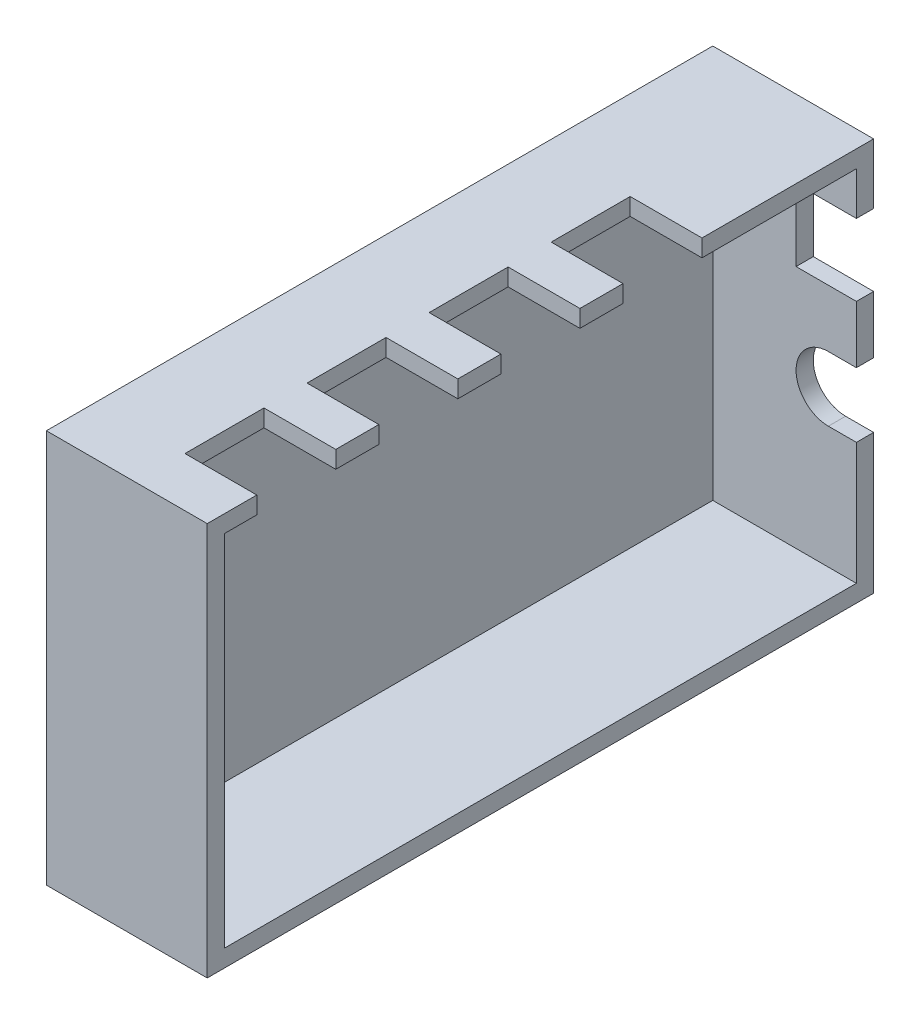
SolidWorks part; units mm, degrees
ref_plane "Front Plane" through (0, 0, 0) normal (0, 0, 1) x (1, 0, 0)
ref_plane "Top Plane" through (0, 0, 0) normal (0, 1, 0) x (1, 0, 0)
ref_plane "Right Plane" through (0, 0, 0) normal (1, 0, 0) x (0, 0, -1)
sketch "Sketch1" plane through (16.0375, 0, 0) normal (-1, 0, 0) x (0, 0, 1)
  line L1 (13.8883, 37.3092) -> (57.8883, 37.3092)
  line L2 (13.8883, 37.3092) -> (13.8883, 12.3092)
  line L3 (13.8883, 12.3092) -> (57.8883, 12.3092)
  line L4 (57.8883, 37.3092) -> (57.8883, 12.3092)
extrude "Boss-Extrude1" add sketch "Sketch1" along normal blind 10
shell "Shell1" thickness 1.2 removed face at (16.0375, 24.8092, 35.8883) outward yes
sketch "Sketch2" plane through (0, 38.5092, 0) normal (0, 1, 0) x (1, 0, 0)
  line L0 (16.0375, -55.6383) -> (21.0375, -55.6383) construction
  line L1 (16.0375, -55.6383) -> (21.0375, -55.6383) construction
  line L2 (21.0375, -50.1383) -> (16.0375, -50.1383) construction
  line L3 (21.0375, -50.1383) -> (16.0375, -50.1383) construction
  line L4 (16.0375, -59.0883) -> (16.0375, -12.6883)
  line L5 (16.0375, -12.6883) -> (4.8375, -12.6883)
  line L6 (4.8375, -12.6883) -> (4.8375, -59.0883)
  line L7 (4.8375, -59.0883) -> (16.0375, -59.0883)
  line L8 (16.0375, -59.0883) -> (16.0375, -12.6883)
  line L9 (16.0375, -12.6883) -> (4.8375, -12.6883)
  line L10 (4.8375, -12.6883) -> (4.8375, -59.0883)
  line L11 (4.8375, -59.0883) -> (16.0375, -59.0883)
  line L12 (21.0375, -41.6383) -> (16.0375, -41.6383) construction
  line L13 (21.0375, -41.6383) -> (16.0375, -41.6383) construction
  line L14 (16.0375, -47.1383) -> (21.0375, -47.1383) construction
  line L15 (16.0375, -47.1383) -> (21.0375, -47.1383) construction
  line L16 (16.0375, -38.6383) -> (21.0375, -38.6383) construction
  line L17 (16.0375, -38.6383) -> (21.0375, -38.6383) construction
  line L18 (21.0375, -33.1383) -> (16.0375, -33.1383) construction
  line L19 (21.0375, -33.1383) -> (16.0375, -33.1383) construction
  line L20 (16.0375, -30.1383) -> (21.0375, -30.1383) construction
  line L21 (16.0375, -30.1383) -> (21.0375, -30.1383) construction
  line L22 (21.0375, -24.6383) -> (16.0375, -24.6383) construction
  line L23 (21.0375, -24.6383) -> (16.0375, -24.6383) construction
  line L24 (16.0375, -55.6383) -> (11.0375, -55.6383)
  line L25 (11.0375, -55.6383) -> (11.0375, -50.1383)
  line L26 (11.0375, -50.1383) -> (16.0375, -50.1383)
  line L27 (16.0375, -47.1383) -> (11.0375, -47.1383)
  line L28 (11.0375, -47.1383) -> (11.0375, -41.6383)
  line L29 (11.0375, -41.6383) -> (16.0375, -41.6383)
  line L30 (16.0375, -38.6383) -> (11.0375, -38.6383)
  line L31 (11.0375, -38.6383) -> (11.0375, -33.1383)
  line L32 (11.0375, -33.1383) -> (16.0375, -33.1383)
  line L33 (16.0375, -30.1383) -> (11.0375, -30.1383)
  line L34 (11.0375, -30.1383) -> (11.0375, -24.6383)
  line L35 (11.0375, -24.6383) -> (16.0375, -24.6383)
  line L36 (16.0375, -30.1383) -> (16.0375, -24.6383)
  line L37 (16.0375, -38.6383) -> (16.0375, -33.1383)
  line L38 (16.0375, -47.1383) -> (16.0375, -41.6383)
  line L39 (16.0375, -55.6383) -> (16.0375, -50.1383)
  dimension "D1" = 0
extrude "Cut-Extrude1" cut sketch "Sketch2" against normal up to surface (1.2 mm away) contours L26 L25 L24 L8 | L29 L28 L27 L8 | L32 L31 L30 L8 | L35 L34 L33 L8 region at (13.5375, 38.5092, 52.8883) region at (13.5375, 38.5092, 44.3883) region at (13.5375, 38.5092, 27.3883) region at (13.5375, 38.5092, 35.8883) up to face at (11.0375, 37.3092, 35.8883)
sketch "Sketch3" plane through (0, 0, 12.6883) normal (0, 0, -1) x (-1, 0, 0)
  line L0 (-16.0375, 34.3092) -> (-20.2375, 34.3092) construction
  line L1 (-16.0375, 34.3092) -> (-20.2375, 34.3092) construction
  line L2 (-20.2375, 29.3092) -> (-16.0375, 29.3092) construction
  line L3 (-20.2375, 29.3092) -> (-16.0375, 29.3092) construction
  line L4 (-16.0375, 25.3092) -> (-17.9875, 25.3092) construction
  line L5 (-16.0375, 25.3092) -> (-17.9875, 25.3092) construction
  line L6 (-17.9875, 20.8092) -> (-16.0375, 20.8092) construction
  line L7 (-17.9875, 20.8092) -> (-16.0375, 20.8092) construction
  line L8 (-16.0375, 34.3092) -> (-11.8375, 34.3092)
  line L9 (-11.8375, 34.3092) -> (-11.8375, 29.3092)
  line L10 (-11.8375, 29.3092) -> (-16.0375, 29.3092)
  line L11 (-16.0375, 29.3092) -> (-16.0375, 34.3092)
  line L12 (-16.0375, 25.3092) -> (-14.0875, 25.3092)
  line L13 (-16.0375, 20.8092) -> (-14.0875, 20.8092)
  line L14 (-16.0375, 25.3092) -> (-16.0375, 20.8092)
  arc A0 (-14.0875, 25.3092) -> (-14.0875, 20.8092) centre (-14.0875, 23.0592) cw
extrude "Cut-Extrude2" cut sketch "Sketch3" against normal up to surface (1.2 mm away) up to face at (11.0375, 24.8092, 13.8883)
